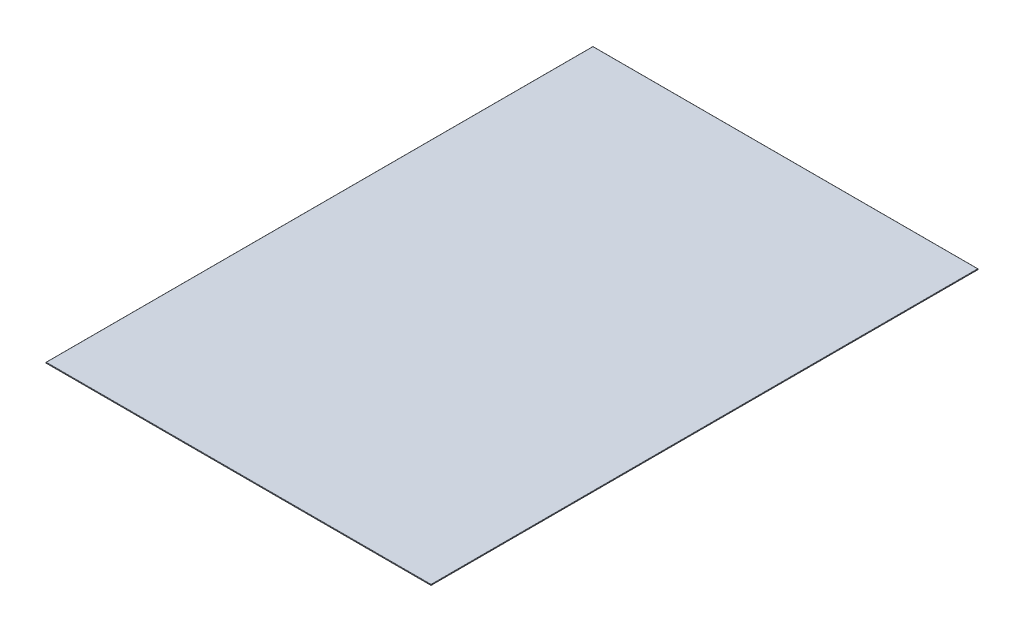
SolidWorks part; units mm, degrees
material "6061-T6 (SS)"
ref_plane "Front Plane" through (0, 0, 0) normal (0, 0, 1) x (1, 0, 0)
ref_plane "Top Plane" through (0, 0, 0) normal (0, 1, 0) x (1, 0, 0)
ref_plane "Right Plane" through (0, 0, 0) normal (1, 0, 0) x (0, 0, -1)
sketch "Sketch1" plane through (0, 0, 0) normal (0, 1, 0) x (1, 0, 0)
  line L1 (0, 0) -> (2000, 0)
  line L2 (0, 0) -> (0, -2000)
  line L3 (0, -2000) -> (2000, -2000)
  line L4 (2000, 0) -> (2000, -2000)
  dimension "D1" = 2000
  dimension "D2" = 2000
extrude "Boss-Extrude1" add sketch "Sketch1" along normal blind 3.175
sketch "Sketch3" plane through (0, 0, 0) normal (0, -1, 0) x (1, 0, 0)
  line L0 (0, 2000) -> (2000, 0) construction
  line L1 (0, 0) -> (2000, 2000) construction
  line L3 (2000, 0) -> (0, 0) construction
  line L5 (2000, 2000) -> (2000, 0) construction
  line L7 (0, 0) -> (0, 2000) construction
  line L9 (0, 2000) -> (2000, 2000) construction
  line L10 (1000, 500) -> (1000, 0) construction
  line L11 (1500, 1000) -> (2000, 1000)
  line L12 (500, 1000) -> (0, 1000)
  line L13 (1000, 1500) -> (1000, 2000)
  point P8 (1000, 1000)
  point P9 (1000, 250)
  point P13 (1000, 500)
  point P23 (1500, 1000)
  point P24 (500, 1000)
  point P25 (1000, 1500)
  point P30 (250, 1000)
  point P31 (1000, 1750)
  point P32 (1750, 1000)
sketch "Sketch4" plane through (0, 3.175, 0) normal (0, 1, 0) x (1, 0, 0)
  line L0 (0, -2000) -> (2000, -2000) construction
  line L1 (0, 0) -> (591.8242, 0)
  line L2 (0, 0) -> (0, -2000)
  line L3 (0, -2000) -> (591.8242, -2000)
  line L4 (591.8242, 0) -> (591.8242, -2000)
extrude "Cut-Extrude1" cut sketch "Sketch4" against normal through all
fillet "Fillet1" radius 1 12 edges at (591.8242, 1.5875, 2000) (2000, 1.5875, 2000) (2000, 1.5875, 0) (591.8242, 1.5875, 0) (1295.9121, 3.175, 0) (2000, 3.175, 1000) (1295.9121, 3.175, 2000) (591.8242, 3.175, 1000) (2000, 0, 1000) (1295.9121, 0, 0) (591.8242, 0, 1000) (1295.9121, 0, 2000)
